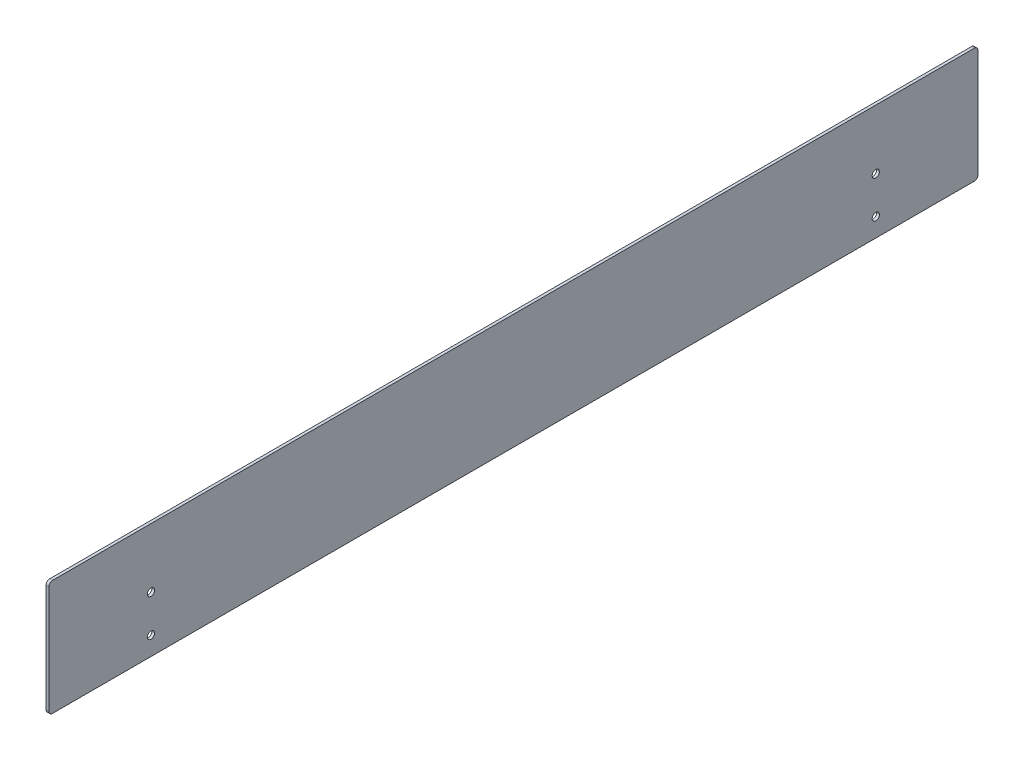
SolidWorks part; units mm, degrees
ref_plane "Front Plane" through (0, 0, 0) normal (0, 0, 1) x (1, 0, 0)
ref_plane "Top Plane" through (0, 0, 0) normal (0, 1, 0) x (1, 0, 0)
ref_plane "Right Plane" through (0, 0, 0) normal (1, 0, 0) x (0, 0, -1)
sketch "Sketch1" plane through (0, 0, 0) normal (1, 0, 0) x (0, 0, -1)
  line L1 (-286.3393, -78.2926) -> (213.6607, -78.2926)
  line L2 (-286.3393, -78.2926) -> (-286.3393, -140.2926)
  line L3 (-286.3393, -140.2926) -> (213.6607, -140.2926)
  line L4 (213.6607, -78.2926) -> (213.6607, -140.2926)
  circle A0 centre (158.6607, -110.2926) radius 1.95
  circle A1 centre (158.6607, -130.2926) radius 1.95
  circle A2 centre (-231.3393, -110.2926) radius 1.95
  circle A3 centre (-231.3393, -130.2926) radius 1.95
  dimension "D3" = 55
  dimension "D1" = 500
  dimension "D2" = 62
  dimension "D4" = 20
  dimension "D5" = 10
  dimension "D6" = 55
  dimension "D7" = 20
  dimension "D8" = 10
extrude "Boss-Extrude1" add sketch "Sketch1" along normal blind 1.5
fillet "Fillet1" radius 2 4 edges at (0.75, -140.2926, -213.6607) (0.75, -78.2926, -213.6607) (0.75, -140.2926, 286.3393) (0.75, -78.2926, 286.3393)
